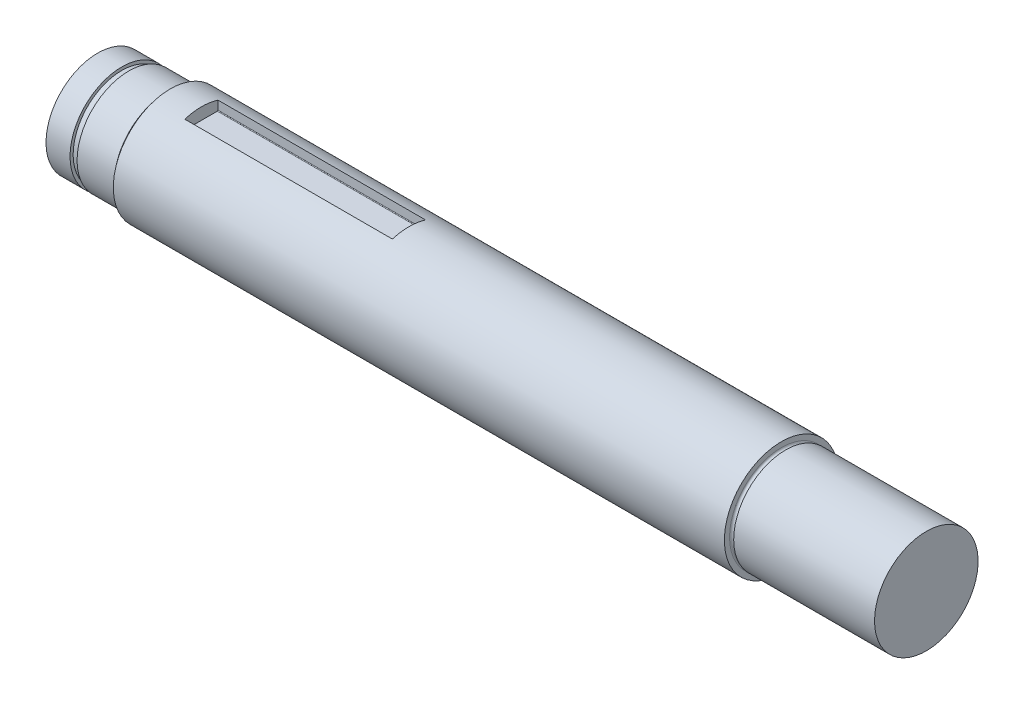
SolidWorks part; units mm, degrees
ref_plane "Front Plane" through (0, 0, 0) normal (0, 0, 1) x (1, 0, 0)
ref_plane "Top Plane" through (0, 0, 0) normal (0, 1, 0) x (1, 0, 0)
ref_plane "Right Plane" through (0, 0, 0) normal (1, 0, 0) x (0, 0, -1)
sketch "Sketch1" plane through (0, 0, 0) normal (1, 0, 0) x (0, 0, -1)
  circle A0 centre (0, 0) radius 25
  circle A1 centre (0, 0) radius 27.5
  dimension "D1" = 50
  dimension "D2" = 55
extrude "Boss-Extrude1" add sketch "Sketch1" along normal mid plane 200 contours A0 | A1 A0 region at (0, 0, 0) region at (0, 0, 26.7222)
extrude "Boss-Extrude2" add sketch "Sketch1<4>" along normal mid plane 350 contours A0 region at (0, 0, 0)
sketch "Sketch1<4>" plane through (0, 0, 0) normal (1, 0, 0) x (0, 0, -1) same geometry as "Sketch1"
sketch "Sketch6" plane through (100, 0, 0) normal (1, 0, 0) x (0, 0, -1)
  circle A0 centre (0, 0) radius 25
  circle A1 centre (0, 0) radius 27.5
  dimension "D1" = 50
  dimension "D2" = 55
extrude "Boss-Extrude4" add sketch "Sketch6" along normal blind 95
sketch "Sketch8" plane through (175, 0, 0) normal (1, 0, 0) x (0, 0, -1)
  circle A0 centre (0, 0) radius 25
  dimension "D1" = 50
extrude "Boss-Extrude5" add sketch "Sketch8" along normal blind 90
sketch "Sketch3" plane through (0, 0, 0) normal (0, 0, 1) x (1, 0, 0)
  line L0 (195, 25) -> (197, 25)
  line L1 (-100, 25) -> (-102, 25)
  line L3 (-100, 0) -> (195, 0) construction
  line L4 (195, 0) -> (-100, 0) construction
  line L6 (195, -25) -> (195, 25) construction
  line L7 (47.5, 0) -> (47.5, 27.5) construction
  line L8 (195, 27.5) -> (-100, 27.5) construction
  line L9 (195, -27.5) -> (195, 27.5) construction
  arc A2 (195, 25) -> (197, 25) centre (196, 25) ccw
  arc A3 (-100, 25) -> (-102, 25) centre (-101, 25) cw
  dimension "D1" = 1
  dimension "D2" = 2
  dimension "D3" = 25
revolve "Cut-Revolve1" cut sketch "Sketch3" angle 360 about L3
sketch "Sketch4" plane through (-100, 0, 0) normal (-1, 0, 0) x (0, 0, 1)
  line L0 (-8, 26.3106) -> (-8, 22.1)
  line L1 (-7.7, 21.8) -> (7.7, 21.8)
  line L2 (8, 22.1) -> (8, 26.3106)
  circle A0 centre (0, 0) radius 27.5 construction
  arc A1 (8, 26.3106) -> (-8, 26.3106) centre (0, 0) ccw
  arc A2 (-8, 22.1) -> (-7.7, 21.8) centre (-7.7, 22.1) ccw
  arc A3 (7.7, 21.8) -> (8, 22.1) centre (7.7, 22.1) ccw
  point P7 (0, 21.8)
  point P9 (0, 27.5)
  point P12 (-8, 21.8)
  point P15 (8, 21.8)
  dimension "D1" = 16
  dimension "D3" = 0.3
  dimension "D2" = 5.7
extrude "Cut-Extrude1" cut sketch "Sketch4" against normal blind 100.215 from offset 15 offset against normal yes
sketch "Sketch10" plane through (-175, 0, 0) normal (-1, 0, 0) x (0, 0, 1)
  circle A0 centre (0, 0) radius 25
  dimension "D1" = 50
extrude "Cut-Extrude3" cut sketch "Sketch10" against normal blind 40
sketch "Sketch11" plane through (-100, 0, 0) normal (-1, 0, 0) x (0, 0, 1)
  circle A0 centre (0, 0) radius 25
  circle A1 centre (0, 0) radius 23.5
  dimension "D1" = 50
  dimension "D2" = 47
extrude "Cut-Extrude4" cut sketch "Sketch11" along normal blind 3.4 from offset 20
